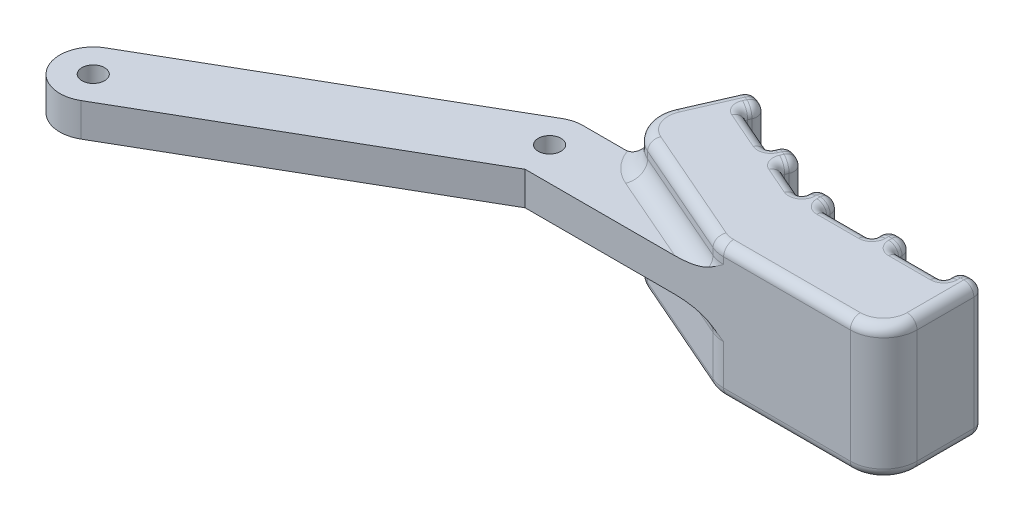
SolidWorks part; units mm, degrees
ref_plane "Front Plane" through (0, 0, 0) normal (0, 0, 1) x (1, 0, 0)
ref_plane "Top Plane" through (0, 0, 0) normal (0, 1, 0) x (1, 0, 0)
ref_plane "Right Plane" through (0, 0, 0) normal (1, 0, 0) x (0, 0, -1)
sketch "Sketch1" plane through (0, 0, 0) normal (0, 1, 0) x (1, 0, 0)
  line L0 (0, 0) -> (50, 0) construction
  line L1 (0, 5) -> (50, 5)
  line L2 (0, -5) -> (50, -5)
  arc A0 (0, 5) -> (0, -5) centre (0, 0) ccw
  arc A1 (50, -5) -> (50, 5) centre (50, 0) ccw
  circle A2 centre (0, 0) radius 1.7
  point P3 (25, 0)
  dimension "D1" = 5
  dimension "D3" = 3.4
  dimension "D2" = 50
extrude "Boss-Extrude1" add sketch "Sketch1" along normal blind 5
sketch "Sketch2" plane through (0, 0, 0) normal (0, -1, 0) x (1, 0, 0)
  line L0 (0, 0) -> (-43.3013, 25) construction
  line L1 (-2.5, -4.3301) -> (-45.8013, 20.6699)
  line L2 (2.5, 4.3301) -> (-40.8013, 29.3301)
  line L3 (0, 0) -> (49.8496, 0) construction
  arc A0 (-2.5, -4.3301) -> (2.5, 4.3301) centre (0, 0) ccw
  arc A1 (-40.8013, 29.3301) -> (-45.8013, 20.6699) centre (-43.3013, 25) ccw
  circle A2 centre (0, 0) radius 1.7
  circle A3 centre (-43.3013, 25) radius 1.7
  point P3 (-21.6506, 12.5)
  dimension "D1" = 5
  dimension "D2" = 3.4
  dimension "D4" = 3.4
  dimension "D3" = 150
  dimension "D5" = 50
extrude "Boss-Extrude2" add sketch "Sketch2" against normal blind 5
sketch "Sketch4" plane through (0, 0, 0) normal (0, -1, 0) x (1, 0, 0)
  line L0 (1.3397, 5) -> (50, 5) construction
  line L1 (31.0436, 5) -> (50, 5)
  line L2 (30, 5) -> (30, -8.5) construction
  line L3 (31.5, -10) -> (32, -10)
  line L4 (55, 0) -> (55, -8.5)
  line L5 (42.25, -10) -> (42.75, -10)
  line L7 (33.5, -8.5) -> (33.5, -8)
  line L8 (34, -7.5) -> (40.25, -7.5)
  line L9 (40.75, -8.5) -> (40.75, -8)
  line L11 (44.25, -8.5) -> (44.25, -8)
  line L12 (44.75, -7.5) -> (51, -7.5)
  line L13 (51.5, -8.5) -> (51.5, -8)
  line L14 (53, -10) -> (53.5, -10)
  line L15 (29.0436, 4.5826) -> (11.6697, -3)
  line L16 (9.0871, -9.5826) -> (12.0697, -16.4165)
  line L17 (30, -8.5) -> (30, -10) construction
  line L18 (30, -10) -> (55, -10) construction
  line L19 (55, -10) -> (55, -8.5) construction
  line L20 (14.0445, -17.1913) -> (14.5027, -16.9913)
  line L21 (15.2775, -15.0165) -> (15.0775, -14.5583)
  line L22 (15.3358, -13.9) -> (21.064, -11.4)
  line L23 (21.7222, -11.6583) -> (21.9222, -12.1165)
  line L24 (25.13, -10.7165) -> (24.93, -10.2583)
  line L25 (25.1883, -9.6) -> (29.3, -7.8055)
  line L26 (34, -7.5) -> (30, -7.5) construction
  line L27 (23.897, -12.8913) -> (24.3553, -12.6913)
  line L28 (30, -8.5) -> (30, -8.2638)
  line L29 (50, -5) -> (0, -5) construction
  arc A0 (50, -5) -> (50, 5) centre (50, 0) ccw construction
  arc A1 (50, 5) -> (55, 0) centre (50, 0) cw
  arc A2 (53.5, -10) -> (55, -8.5) centre (53.5, -8.5) ccw
  arc A3 (53, -10) -> (51.5, -8.5) centre (53, -8.5) cw
  arc A4 (42.75, -10) -> (44.25, -8.5) centre (42.75, -8.5) ccw
  arc A5 (42.25, -10) -> (40.75, -8.5) centre (42.25, -8.5) cw
  arc A6 (32, -10) -> (33.5, -8.5) centre (32, -8.5) ccw
  arc A7 (30, -8.5) -> (31.5, -10) centre (31.5, -8.5) ccw
  arc A8 (51, -7.5) -> (51.5, -8) centre (51, -8) cw
  arc A9 (44.25, -8) -> (44.75, -7.5) centre (44.75, -8) cw
  arc A10 (40.25, -7.5) -> (40.75, -8) centre (40.25, -8) cw
  arc A11 (33.5, -8) -> (34, -7.5) centre (34, -8) cw
  arc A12 (29.3, -7.8055) -> (30, -8.2638) centre (29.5, -8.2638) cw
  arc A13 (24.93, -10.2583) -> (25.1883, -9.6) centre (25.3883, -10.0583) cw
  arc A14 (21.064, -11.4) -> (21.7222, -11.6583) centre (21.264, -11.8583) cw
  arc A15 (15.0775, -14.5583) -> (15.3358, -13.9) centre (15.5358, -14.3583) cw
  arc A16 (25.13, -10.7165) -> (24.3553, -12.6913) centre (23.7553, -11.3165) cw
  arc A17 (21.9222, -12.1165) -> (23.897, -12.8913) centre (23.297, -11.5165) ccw
  arc A18 (15.2775, -15.0165) -> (14.5027, -16.9913) centre (13.9027, -15.6165) cw
  arc A19 (12.0697, -16.4165) -> (14.0445, -17.1913) centre (13.4445, -15.8165) ccw
  arc A20 (31.0436, 5) -> (29.0436, 4.5826) centre (31.0436, 0) ccw
  arc A21 (11.6697, -3) -> (9.0871, -9.5826) centre (13.6697, -7.5826) ccw
  point P16 (44.25, -8.25)
  point P22 (55, 5)
  point P24 (55, -10)
  point P27 (51.5, -10)
  point P30 (44.25, -10)
  point P35 (33.5, -10)
  point P40 (51.5, -7.5)
  point P43 (44.25, -7.5)
  point P46 (40.75, -7.5)
  point P49 (33.5, -7.5)
  point P67 (24.73, -9.8)
  point P70 (21.5222, -11.2)
  point P73 (14.8775, -14.1)
  point P76 (25.73, -12.0913)
  point P79 (22.5222, -13.4913)
  point P82 (15.8775, -16.3913)
  point P85 (12.6697, -17.7913)
  point P91 (7.0871, -5)
  dimension "D9" = 5
  dimension "D10" = 1.5
  dimension "D11" = 0.5
  dimension "D19" = 0.5
  dimension "D20" = 1.5
  dimension "D21" = 5
  dimension "D1" = 25
  dimension "D2" = 15
  dimension "D3" = 3.5
  dimension "D4" = 7.25
  dimension "D5" = 7.25
  dimension "D6" = 3.5
  dimension "D7" = 2.5
  dimension "D8" = 2.5
  dimension "D12" = 25
  dimension "D13" = 2.5
  dimension "D14" = 2.5
  dimension "D15" = 2.5
  dimension "D16" = 3.5
  dimension "D17" = 3.5
  dimension "D18" = 7.25
extrude "Boss-Extrude3" add sketch "Sketch4" along normal blind 10 and the other way blind 10
fillet "Fillet1" radius 2.5 7 edges at (9.3883, 2.5, -5) (10.3736, 5, -3.8228) (30.022, 5, 4.8945) (10.3736, 0, -3.8228) (30.022, 0, 4.8945) (20.3566, 5, 0.7913) (20.3566, 0, 0.7913)
fillet "Fillet2" radius 1.5 84 edges at (24.9228, 10, -9.8756) (25.03, 10, -10.4874) (25.1516, 10, -11.8644) (24.1261, 10, -12.7913) (22.7492, 10, -12.9129) (21.8222, 10, -11.8874) (21.4466, 10, -11.3928) (18.1999, 10, -12.65) (15.0703, 10, -14.1756) (15.1775, 10, -14.7874) (15.2991, 10, -16.1644) (14.2736, 10, -17.0913) (12.8966, 10, -17.2129) (10.5784, 10, -12.9995) (9.0151, 10, -5.7564) (20.3566, 10, 0.7913) (30.022, 10, 4.8945) (40.5218, 10, 5) (53.5355, 10, 3.5355) (55, 10, -4.25) (54.5607, 10, -9.5607) (53.25, 10, -10) (51.9393, 10, -9.5607) (51.5, 10, -8.25) (51.3536, 10, -7.6464) (47.875, 10, -7.5) (44.3964, 10, -7.6464) (44.25, 10, -8.25) (43.8107, 10, -9.5607) (42.5, 10, -10) (41.1893, 10, -9.5607) (40.75, 10, -8.25) (40.6036, 10, -7.6464) (37.125, 10, -7.5) (33.6464, 10, -7.6464) (33.5, 10, -8.25) (33.0607, 10, -9.5607) (31.75, 10, -10) (30.4393, 10, -9.5607) (30, 10, -8.3819) (29.7739, 10, -7.8454) (53.5355, -10, 3.5355) (55, -10, -4.25) (54.5607, -10, -9.5607) (53.25, -10, -10) (51.9393, -10, -9.5607) (51.5, -10, -8.25) (51.3536, -10, -7.6464) (47.875, -10, -7.5) (44.3964, -10, -7.6464) (44.25, -10, -8.25) (43.8107, -10, -9.5607) (42.5, -10, -10) (41.1893, -10, -9.5607) (40.75, -10, -8.25) (40.6036, -10, -7.6464) (37.125, -10, -7.5) (33.6464, -10, -7.6464) (33.5, -10, -8.25) (33.0607, -10, -9.5607) (31.75, -10, -10) (30.4393, -10, -9.5607) (30, -10, -8.3819) (29.7739, -10, -7.8454) (27.2441, -10, -8.7028) (24.9228, -10, -9.8756) (25.03, -10, -10.4874) (25.1516, -10, -11.8644) (24.1261, -10, -12.7913) (22.7492, -10, -12.9129) (21.8222, -10, -11.8874) (21.4466, -10, -11.3928) (18.1999, -10, -12.65) (15.0703, -10, -14.1756) (15.1775, -10, -14.7874) (15.2991, -10, -16.1644) (14.2736, -10, -17.0913) (12.8966, -10, -17.2129) (10.5784, -10, -12.9995) (9.0151, -10, -5.7564) (20.3566, -10, 0.7913) (30.022, -10, 4.8945) (27.2441, 10, -8.7028) (40.5218, -10, 5)
